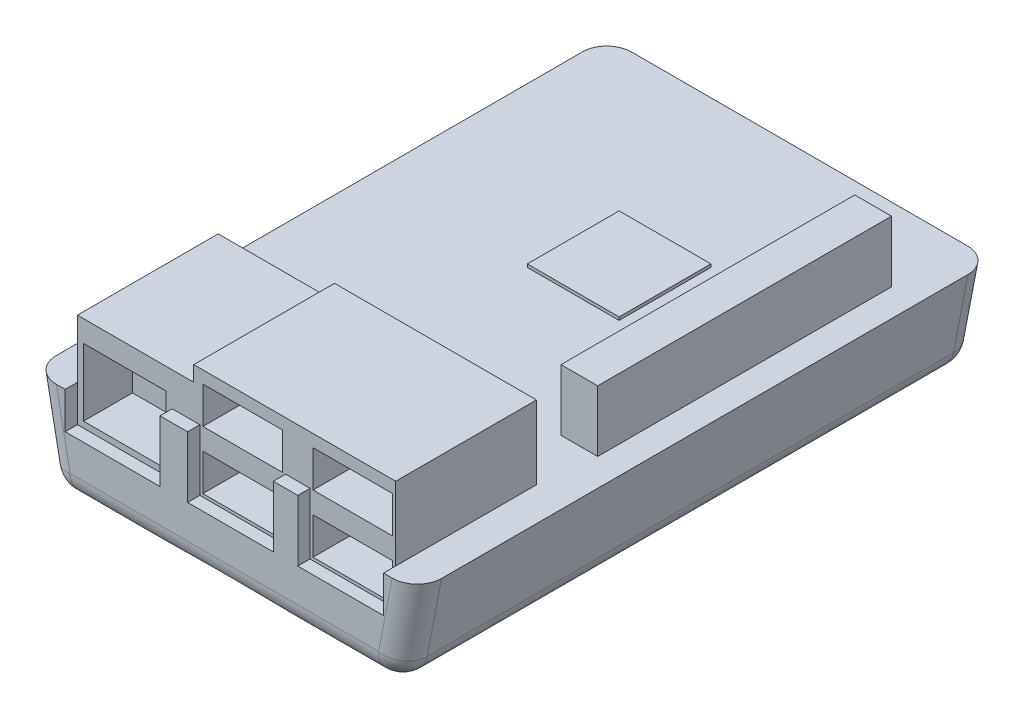
SolidWorks part; units mm, degrees
ref_plane "Front Plane" through (0, 0, 0) normal (0, 0, 1) x (1, 0, 0)
ref_plane "Top Plane" through (0, 0, 0) normal (0, 1, 0) x (1, 0, 0)
ref_plane "Right Plane" through (0, 0, 0) normal (1, 0, 0) x (0, 0, -1)
sketch "Sketch1" plane through (0, 0, 0) normal (0, 0, 1) x (1, 0, 0)
  line L0 (0, 0) -> (13.5493, 0) construction
  line L1 (-28.5, 0) -> (28.5, 0)
  line L2 (28.5, 0) -> (31.5, 15.5)
  line L3 (31.5, 15.5) -> (-31.5, 15.5)
  line L4 (-31.5, 15.5) -> (-28.5, 0)
  line L5 (0, 15.5) -> (0, 0) construction
  line L6 (0, -123.2234) -> (0, 0) construction
  line L7 (21, 0) -> (21, 15.5) construction
  circle A0 centre (0, -123.2234) radius 125
  point P6 (0, 0)
  dimension "D4" = 250
  dimension "D1" = 57
  dimension "D2" = 63
  dimension "D3" = 15.5
  dimension "D5" = 7.5
extrude "Boss-Extrude1" add sketch "Sketch1" along normal blind 94 contours A0 L1 L2 L3 L4
sketch "Sketch2" plane through (0, 0, 0) normal (0, 0, -1) x (-1, 0, 0)
  line L1 (-7, -7) -> (7, -7)
  line L2 (-7, -7) -> (-7, 7)
  line L3 (-7, 7) -> (7, 7)
  line L4 (7, -7) -> (7, 7)
  line L5 (-7, -7) -> (7, 7) construction
  line L6 (-7, 7) -> (7, -7) construction
  point P0 (0, 0)
  dimension "D1" = 14
  dimension "D2" = 7
extrude "Cut-Extrude1" cut sketch "Sketch2" against normal blind 5
sketch "Sketch3" plane through (0, 0, 94) normal (0, 0, 1) x (1, 0, 0)
  line L0 (31.5, 15.5) -> (-31.5, 15.5) construction
  line L1 (26, 15.5) -> (-26, 15.5)
  line L2 (26, 15.5) -> (26, 27.5)
  line L3 (26, 27.5) -> (-26, 27.5)
  line L4 (-26, 15.5) -> (-26, 27.5)
  line L5 (21, 0) -> (28.5, 0) construction
  line L6 (0, 27.5) -> (0, 0) construction
  dimension "D1" = 27.5
  dimension "D2" = 52
extrude "Boss-Extrude2" add sketch "Sketch3" against normal blind 25
sketch "Sketch4" plane through (0, 15.5, 0) normal (0, 1, 0) x (1, 0, 0)
  line L0 (31.5, 0) -> (-31.5, 0) construction
  line L1 (21, -12) -> (27, -12)
  line L2 (21, -12) -> (21, -60)
  line L3 (21, -60) -> (27, -60)
  line L4 (27, -12) -> (27, -60)
  line L5 (31.5, -94) -> (31.5, 0) construction
  dimension "D1" = 6
  dimension "D2" = 48
  dimension "D3" = 12
  dimension "D4" = 4.5
extrude "Boss-Extrude3" add sketch "Sketch4" along normal blind 10
sketch "Sketch5" plane through (0, 0, 94) normal (0, 0, 1) x (1, 0, 0)
  line L0 (-28.5, 0) -> (-21, 0) construction
  line L1 (-25, 21.5) -> (-11.5, 21.5)
  line L2 (-25, 21.5) -> (-25, 10.5)
  line L3 (-25, 10.5) -> (-11.5, 10.5)
  line L4 (-11.5, 21.5) -> (-11.5, 10.5)
  line L5 (-5.5, 25.5) -> (7.5, 25.5)
  line L6 (-5.5, 25.5) -> (-5.5, 19.5)
  line L7 (-5.5, 19.5) -> (7.5, 19.5)
  line L8 (7.5, 25.5) -> (7.5, 19.5)
  line L9 (12.5, 25.5) -> (25.5, 25.5)
  line L10 (12.5, 25.5) -> (12.5, 19.5)
  line L11 (12.5, 19.5) -> (25.5, 19.5)
  line L12 (25.5, 25.5) -> (25.5, 19.5)
  line L13 (-5.5, 16) -> (7.5, 16)
  line L14 (-5.5, 16) -> (-5.5, 10)
  line L15 (-5.5, 10) -> (7.5, 10)
  line L16 (7.5, 16) -> (7.5, 10)
  line L17 (12.5, 16) -> (25.5, 16)
  line L18 (12.5, 16) -> (12.5, 10)
  line L19 (12.5, 10) -> (25.5, 10)
  line L20 (25.5, 16) -> (25.5, 10)
  line L21 (12.5, 19.5) -> (12.5, 16) construction
  line L22 (-5.5, 19.5) -> (-5.5, 16) construction
  line L23 (7.5, 25.5) -> (12.5, 25.5) construction
  line L24 (12.5, 25.5) -> (12.3408, 25.5965) construction
  line L25 (7.5, 10) -> (12.5, 10) construction
  point P20 (-24.75, 0)
  dimension "D1" = 13.5
  dimension "D2" = 11
  dimension "D3" = 10.5
  dimension "D4" = 6.5
  dimension "D5" = 13
  dimension "D6" = 6
  dimension "D7" = 6
  dimension "D8" = 3.5
  dimension "D9" = 10
  dimension "D10" = 5
extrude "Cut-Extrude2" cut sketch "Sketch5" against normal blind 10
sketch "Sketch6" plane through (0, 0, 94) normal (0, 0, 1) x (1, 0, 0)
  line L0 (-26, 15.5) -> (-26, 9.5)
  line L1 (-26, 9.5) -> (-10.5, 9.5)
  line L2 (-10.5, 9.5) -> (-10.5, 19.5)
  line L3 (-10.5, 19.5) -> (-6, 19.5)
  line L4 (-6, 19.5) -> (-6, 9.5)
  line L5 (-6, 9.5) -> (8, 9.5)
  line L6 (8, 9.5) -> (8, 19.5)
  line L7 (8, 19.5) -> (12, 19.5)
  line L8 (12, 19.5) -> (12, 9.5)
  line L9 (12, 9.5) -> (26, 9.5)
  line L10 (26, 9.5) -> (26, 33.9542)
  line L11 (26, 33.9542) -> (-26, 33.9542)
  line L12 (-26, 33.9542) -> (-26, 15.5)
  line L13 (-25, 10.5) -> (-11.5, 10.5) construction
  line L14 (-10.5, 9.5) -> (-6, 9.5) construction
  line L15 (8, 9.5) -> (12, 9.5) construction
  line L20 (26, 15.5) -> (26, 9.5) construction
  line L21 (-6, 19.5) -> (8, 19.5) construction
  line L22 (-11.5, 10.5) -> (-11.5, 21.5) construction
  line L23 (-5.5, 25.5) -> (-5.5, 19.5) construction
  line L24 (7.5, 19.5) -> (7.5, 25.5) construction
  line L25 (12.5, 25.5) -> (12.5, 19.5) construction
  point P20 (-5.5, 22.5)
  dimension "D1" = 1
  dimension "D2" = 10
  dimension "D3" = 1
  dimension "D4" = 0.5
  dimension "D5" = 0.5
  dimension "D6" = 0.5
extrude "Cut-Extrude3" cut sketch "Sketch6" against normal blind 2
sketch "Sketch7" plane through (0, 0, 92) normal (0, 0, 1) x (1, 0, 0)
  line L1 (-26, 27.5) -> (-7, 27.5)
  line L2 (-26, 27.5) -> (-26, 25)
  line L3 (-26, 25) -> (-7, 25)
  line L4 (-7, 27.5) -> (-7, 25)
  dimension "D1" = 19
  dimension "D2" = 2.5
extrude "Cut-Extrude4" cut sketch "Sketch7" against normal through all
sketch "Sketch8" plane through (0, 0, 0) normal (0, -1, 0) x (1, 0, 0)
  line L0 (0, 94) -> (0, 0) construction
  line L1 (21, 94) -> (-21, 94) construction
  line L2 (-20, 54) -> (0, 54) construction
  line L3 (-20, 54) -> (-20, 40) construction
  line L4 (-21, 0) -> (-7, 0) construction
  line L5 (-24, 54) -> (-24, 40)
  line L6 (-16, 40) -> (-16, 54)
  line L7 (24, 54) -> (24, 40)
  line L8 (16, 40) -> (16, 54)
  circle A0 centre (-20, 54) radius 4
  circle A1 centre (-20, 40) radius 4
  circle A2 centre (20, 40) radius 4
  circle A3 centre (20, 54) radius 4
  line M6 (-21, 0) -> (-21, 94)
  dimension "D1" = 8
  dimension "D2" = 20
  dimension "D3" = 40
  dimension "D4" = 40
extrude "Cut-Extrude5" cut sketch "Sketch8" against normal blind 10 contours A0 M6 | A1 M6 | A1 L6 A0 M6 | A1 A0 L5 M6 | A1 M6 | A3 | L7 A3 L8 A2 | A2
sketch "Sketch9" plane through (0, 0, 0) normal (0, -1, 0) x (1, 0, 0)
  line L1 (-16, 40) -> (-16, 54) construction
  line L2 (-15, 40) -> (-15, 54)
  line L3 (-15, 40) -> (-15, 54)
  line L4 (-16, 44.75) -> (-16, 54)
  line L5 (-21, 57.873) -> (-21, 58.899)
  line L6 (-21, 94) -> (-21, 57.873) construction
  line L7 (-16, 44.75) -> (-18.25, 44.75)
  line L8 (-18.25, 44.75) -> (-18.25, 40)
  line L9 (-21.75, 40) -> (-21.75, 44.75)
  line L10 (-21.75, 44.75) -> (-25, 44.75)
  line L11 (-25, 44.75) -> (-25, 40)
  line L12 (-21.75, 44.75) -> (-18.25, 44.75) construction
  line L13 (0, 0) -> (0, 166.6678) construction
  line L14 (16, 44.75) -> (18.25, 44.75)
  line L15 (18.25, 44.75) -> (18.25, 40)
  line L16 (21.75, 40) -> (21.75, 44.75)
  line L17 (21.75, 44.75) -> (25, 44.75)
  line L18 (25, 44.75) -> (25, 40)
  line L19 (15, 40) -> (15, 54)
  line L20 (16, 44.75) -> (16, 54)
  line L21 (21, 57.873) -> (21, 58.899)
  arc A2 (-16, 54) -> (-21, 57.873) centre (-20, 54) ccw construction
  arc A3 (-16, 54) -> (-21, 57.873) centre (-20, 54) ccw
  arc A4 (-25, 40) -> (-15, 40) centre (-20, 40) ccw
  arc A5 (-15, 54) -> (-21.25, 58.8412) centre (-20, 54) ccw
  arc A6 (-25, 40) -> (-15, 40) centre (-20, 40) ccw
  arc A7 (-15, 54) -> (-21, 58.899) centre (-20, 54) ccw
  arc A8 (-21.75, 40) -> (-18.25, 40) centre (-20, 40) ccw
  arc A9 (21.75, 40) -> (18.25, 40) centre (20, 40) cw
  arc A10 (25, 40) -> (15, 40) centre (20, 40) cw
  arc A11 (16, 54) -> (21, 57.873) centre (20, 54) cw
  arc A12 (15, 54) -> (21, 58.899) centre (20, 54) cw
  dimension "D2" = 3.5
  dimension "D3" = 6.5
  dimension "D1" = 1
extrude "Boss-Extrude5" add sketch "Sketch9" against normal blind 2
fillet "Fillet2" radius 4 2 edges at (-28.5, 0, 47) (28.5, 0, 47)
fillet "Fillet3" radius 4 11 edges at (-27.7455, 0.9145, 94) (-27.7455, 0.9145, 0) (23.1, 0, 0) (23.1, 0, 94) (27.7455, 0.9145, 94) (27.7455, 0.9145, 0) (-30.3135, 9.37, 0) (-30.3135, 9.37, 94) (30.3135, 9.37, 94) (30.3135, 9.37, 0) (-23.1, 0, 0)
sketch "Sketch10" plane through (0, 15.5, 0) normal (0, 1, 0) x (1, 0, 0)
  line L0 (-31.5, -90) -> (-31.5, -4) construction
  line L1 (-5.5, -39) -> (9.5, -39)
  line L2 (-5.5, -39) -> (-5.5, -24)
  line L3 (-5.5, -24) -> (9.5, -24)
  line L4 (9.5, -39) -> (9.5, -24)
  line L5 (-5.5, -39) -> (9.5, -24) construction
  line L6 (-5.5, -24) -> (9.5, -39) construction
  line L7 (27.4258, 0) -> (-27.4258, 0) construction
  point P0 (2, -31.5)
  dimension "D1" = 15
  dimension "D2" = 15
  dimension "D3" = 26
  dimension "D4" = 24
extrude "Boss-Extrude6" add sketch "Sketch10" along normal blind 0.5 contours L3 L4 L1 L2
